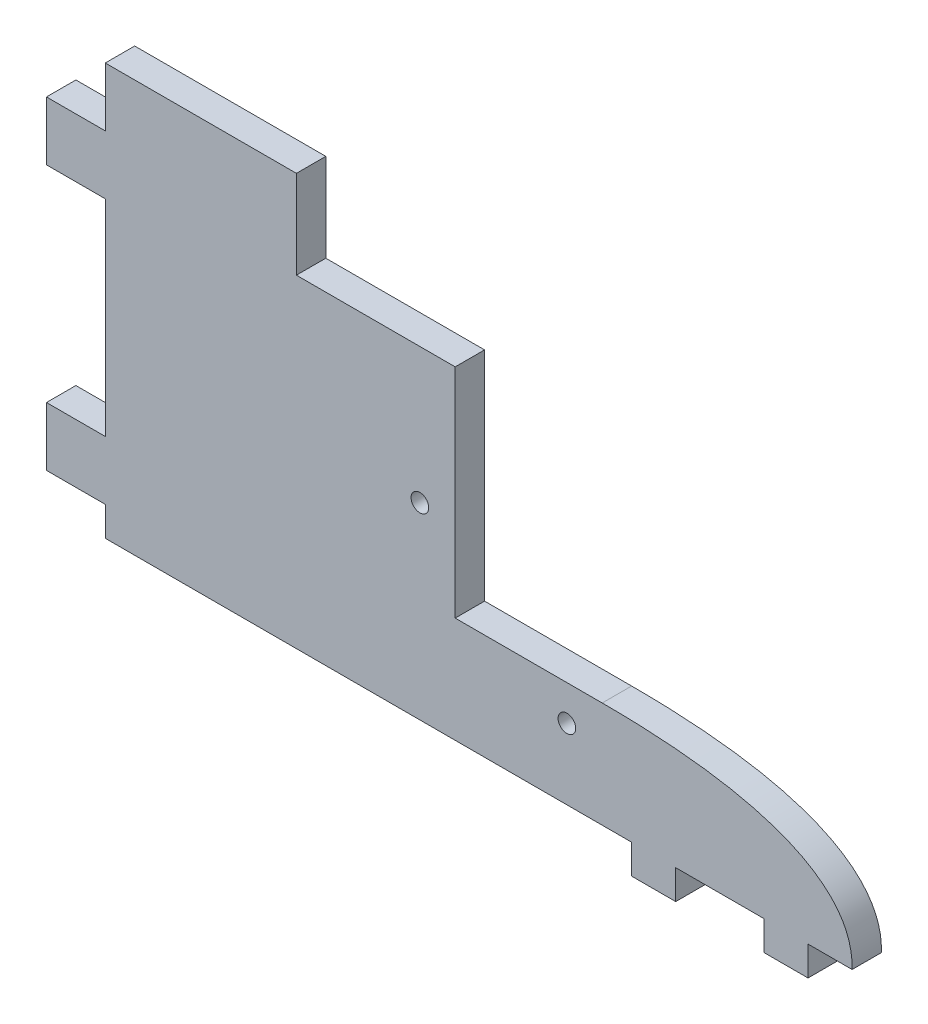
SolidWorks part; units mm, degrees
ref_plane "Plan de face" through (0, 0, 0) normal (0, 0, 1) x (1, 0, 0)
ref_plane "Plan de dessus" through (0, 0, 0) normal (0, 1, 0) x (1, 0, 0)
ref_plane "Plan de droite" through (0, 0, 0) normal (1, 0, 0) x (0, 0, -1)
sketch "Esquisse1" plane through (0, 0, 0) normal (0, 0, 1) x (1, 0, 0)
  line L1 (0, 0) -> (37, 0)
  line L2 (0, 0) -> (0, 55)
  line L3 (0, 55) -> (12, 55)
  line L4 (37, 0) -> (37, 18)
  line L6 (12, 55) -> (12, 18)
  line L7 (12, 18) -> (37, 18)
  circle A0 centre (6, 32) radius 1.5
  circle A1 centre (31, 12) radius 1.5
  dimension "D3" = 20
  dimension "D4" = 3
  dimension "D1" = 6
  dimension "D2" = 55
  dimension "D5" = 12
  dimension "D7" = 25
  dimension "D8" = 6
  dimension "D9" = 6
extrude "Boss.-Extru.1" add sketch "Esquisse1" along normal blind 5
sketch "Esquisse2" plane through (0, 0, 5) normal (0, 0, 1) x (1, 0, 0)
  line L0 (37, 18) -> (12, 18) construction
  line L1 (37, 0) -> (42, 0)
  line L2 (37, 0) -> (37, 18)
  line L3 (49.5, 0) -> (64.5, 0)
  line L4 (12, 55) -> (0, 55) construction
  line L5 (72, 0) -> (72, -5)
  line L6 (72, -5) -> (64.5, -5)
  line L7 (64.5, 0) -> (64.5, -5)
  line L8 (72, 0) -> (79.5, 0)
  line L9 (49.5, 0) -> (49.5, -5)
  line L10 (49.5, -5) -> (42, -5)
  line L11 (42, 0) -> (42, -5)
  line L12 (0, 0) -> (-47.5, 0)
  line L13 (0, 0) -> (0, 55)
  line L14 (0, 55) -> (-15, 55)
  line L15 (-47.5, 60) -> (-47.5, 70)
  line L16 (-47.5, 5) -> (-57.5, 5)
  line L17 (-47.5, 15) -> (-47.5, 50)
  line L18 (-15, 55) -> (-15, 70)
  line L19 (-47.5, 15) -> (-57.5, 15)
  line L20 (-47.5, 0) -> (-47.5, 5)
  line L21 (-57.5, 5) -> (-57.5, 15)
  line L22 (-47.5, 60) -> (-57.5, 60)
  line L24 (-47.5, 50) -> (-57.5, 50)
  line L25 (-57.5, 60) -> (-57.5, 50)
  line L36 (-47.5, 70) -> (-15, 70)
  spline S0 degree 3 poles (37, 18) (79.2395, 18) (79.5, 3.8743) (79.5, 0) knots 0 0 0 0 1 1 1 1
  dimension "D1" = 42.5
  dimension "D2" = 7.5
  dimension "D3" = 5
  dimension "D4" = 5
  dimension "D5" = 15
  dimension "D6" = 15
  dimension "D7" = 70
  dimension "D8" = 10
  dimension "D9" = 5
  dimension "D10" = 35
  dimension "D11" = 10
  dimension "D12" = 47.5
extrude "Boss.-Extru.2" add sketch "Esquisse2" against normal blind 5
